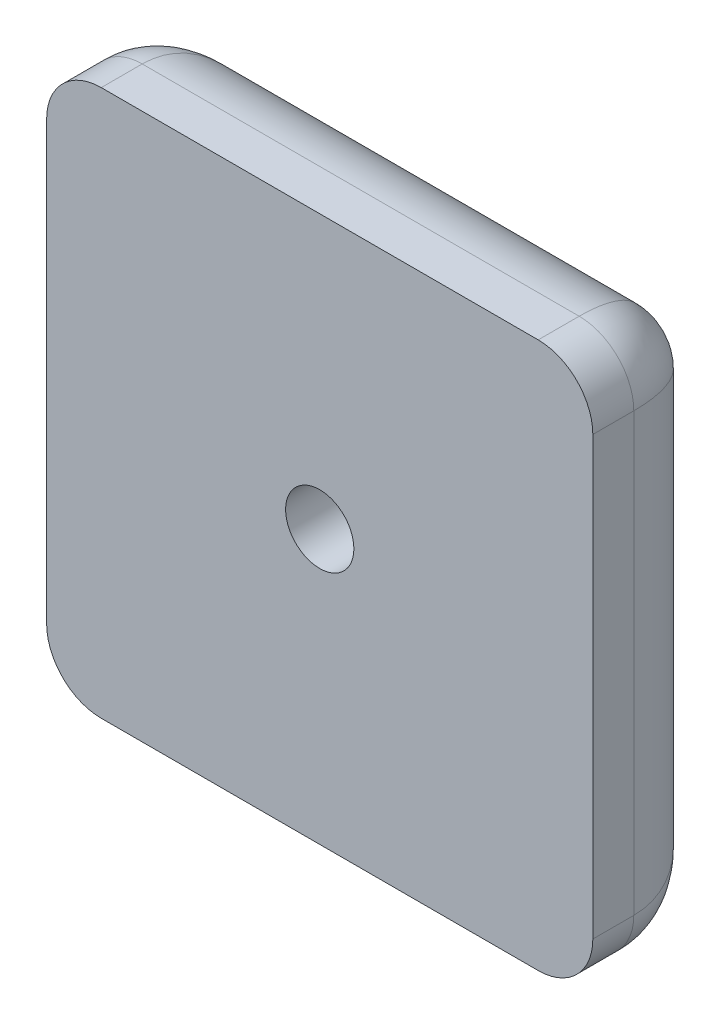
SolidWorks part; units mm, degrees
ref_plane "Ön Düzlem" through (0, 0, 0) normal (0, 0, 1) x (1, 0, 0)
ref_plane "Üst Düzlem" through (0, 0, 0) normal (0, 1, 0) x (1, 0, 0)
ref_plane "Sağ Düzlem" through (0, 0, 0) normal (1, 0, 0) x (0, 0, -1)
sketch "Sketch1" plane through (0, 0, 0) normal (0, 0, 1) x (1, 0, 0)
  line L1 (-20, -20) -> (20, -20)
  line L2 (-20, -20) -> (-20, 20)
  line L3 (-20, 20) -> (20, 20)
  line L4 (20, -20) -> (20, 20)
  line L5 (-20, -20) -> (20, 20) construction
  line L6 (-20, 20) -> (20, -20) construction
  circle A0 centre (0, 0) radius 2.5
  point P0 (0, 0)
  dimension "D1" = 5
  dimension "D2" = 40
  dimension "D3" = 40
extrude "Boss-Extrude1" add sketch "Sketch1" along normal blind 10
fillet "Fillet1" radius 7 4 edges at (0, 20, 0) (0, -20, 0) (20, 0, 0) (-20, 0, 0)
sketch "Sketch2" plane through (0, 0, 0) normal (0, 0, -1) x (-1, 0, 0)
  circle A0 centre (0, 0) radius 4
  dimension "D1" = 8
extrude "Cut-Extrude1" cut sketch "Sketch2" against normal blind 5
fillet "Fillet2" radius 4 8 edges at (17.9497, 17.9497, 2.0503) (17.9497, -17.9497, 2.0503) (-17.9497, -17.9497, 2.0503) (-17.9497, 17.9497, 2.0503) (20, 20, 8.5) (20, -20, 8.5) (-20, -20, 8.5) (-20, 20, 8.5)
